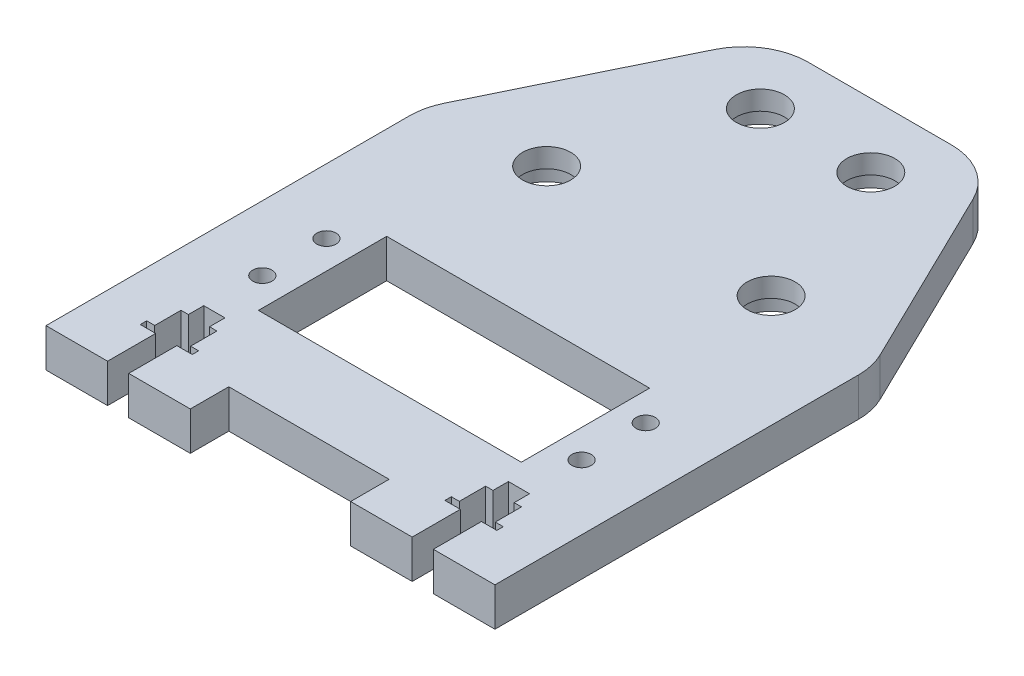
SolidWorks part; units mm, degrees
material "Acrylic (Medium-high impact)"
ref_plane "Front Plane" through (0, 0, 0) normal (0, 0, 1) x (1, 0, 0)
ref_plane "Top Plane" through (0, 0, 0) normal (0, 1, 0) x (1, 0, 0)
ref_plane "Right Plane" through (0, 0, 0) normal (1, 0, 0) x (0, 0, -1)
sketch "Sketch1" plane through (0, 0, 0) normal (0, 1, 0) x (1, 0, 0)
  line L0 (0, 16.0328) -> (0, -11.4098) construction
  line L1 (-38.0739, 0) -> (41.7971, 0) construction
  line L2 (8.6075, -9.22) -> (17.5, -33.652) construction
  line L3 (-8.6075, -9.22) -> (-17.5, -33.652) construction
  line L4 (17.5, -33.652) -> (10.3, -65.6008) construction
  line L5 (24.8896, -70.6008) -> (-24.8896, -70.6008) construction
  line L6 (-17.4416, 0.78) -> (-35, -35.22)
  line L7 (-35, -94.22) -> (35, -94.22)
  line L8 (-35, -94.22) -> (-35, 0.78)
  line L9 (-35, 0.78) -> (35, 0.78)
  line L10 (35, -94.22) -> (35, 0.78)
  line L11 (-35, -94.22) -> (35, 0.78) construction
  line L12 (-35, 0.78) -> (35, -94.22) construction
  line L13 (17.4416, 0.78) -> (35, -35.22)
  line L15 (-12.5, -88.22) -> (12.5, -88.22)
  line L16 (-12.5, -88.22) -> (-12.5, -94.22)
  line L17 (-12.5, -94.22) -> (12.5, -94.22)
  line L18 (12.5, -88.22) -> (12.5, -94.22)
  line L19 (-12.5, -88.22) -> (12.5, -94.22) construction
  line L20 (-12.5, -94.22) -> (12.5, -88.22) construction
  line L21 (20.5, -55.6008) -> (-20.5, -55.6008)
  line L22 (20.5, -55.6008) -> (20.5, -75.6008)
  line L23 (20.5, -75.6008) -> (-20.5, -75.6008)
  line L24 (-20.5, -55.6008) -> (-20.5, -75.6008)
  line L25 (20.5, -55.6008) -> (-20.5, -75.6008) construction
  line L26 (20.5, -75.6008) -> (-20.5, -55.6008) construction
  circle A0 centre (17.5, -33.652) radius 23.625 construction
  circle A1 centre (-8.6075, -9.22) radius 3.75
  circle A2 centre (-17.5, -33.652) radius 3.75
  circle A3 centre (17.5, -33.652) radius 3.75
  circle A4 centre (8.6075, -9.22) radius 3.75
  circle A5 centre (10.3, -65.6008) radius 3.75
  circle A6 centre (8.6075, -9.22) radius 5.5
  circle A7 centre (-8.6075, -9.22) radius 5.5
  circle A8 centre (-17.5, -33.652) radius 5.5
  circle A9 centre (17.5, -33.652) radius 5.5
  point P18 (0, -46.72)
  point P28 (0, -91.22)
  point P37 (0, -65.6008)
  arc B0 (3.9, -65.6008) -> (16.7, -65.6008) centre (10.3, -65.6008) ccw construction
  arc B1 (26.7, -59.3508) -> (22.6896, -60.6008) centre (24.8896, -60.6008) ccw construction
  arc B2 (22.6896, -70.6008) -> (26.7, -71.8508) centre (24.8896, -70.6008) ccw construction
  arc B3 (-26.7, -61.8508) -> (-26.7, -59.3508) centre (-24.8896, -60.6008) ccw construction
  arc B4 (-26.7, -71.8508) -> (-26.7, -69.3508) centre (-24.8896, -70.6008) ccw construction
  circle B5 centre (10.3, -65.6008) radius 6.5
  circle B6 centre (24.8896, -60.6008) radius 1.5
  circle B7 centre (24.8896, -70.6008) radius 1.5
  circle B8 centre (-24.8896, -70.6008) radius 1.5
  circle B9 centre (-24.8896, -60.6008) radius 1.5
  dimension "D5" = 47.25
  dimension "D7" = 7.5
  dimension "D15" = 11
  dimension "D1" = 35
  dimension "D2" = 26
  dimension "D3" = 160
  dimension "D4" = 9.22
  dimension "D6" = 32.75
  dimension "D8" = 95
  dimension "D9" = 70
  dimension "D10" = 10
  dimension "D11" = 26
  dimension "D12" = 59
  dimension "D13" = 25
  dimension "D14" = 6
  dimension "D16" = 41
  dimension "D17" = 20
  dimension "D18" = 10.3
sketch_block_instance "Block1-1"
sketch_block "Block1" parameters "D1"=3, "D2"=13
ref_axis "Axis1" through (17.5, 0, 33.652) along (0, 1, 0)
ref_axis "Axis2" through (-17.5, -6.1694, 33.652) along (0, 1, 0)
ref_axis "Axis3" through (10.3, 0, 65.6008) along (0, 1, 0)
extrude "Boss-Extrude1" add sketch "Sketch1" along normal blind 6 contours L15 L18 L7 L10 L13 L9 L6 L8 L16 B9 B8 B7 B6 B5 A4 A3 A2 A1 | B5 A5 | L21 L24 L23 L22 B9 B8 B5 region at (0, 0, 48.7374) region at (-1.9892, 0, 65.6008) region at (3.9838, 0, 65.6008)
fillet "Fillet1" radius 10 4 edges at (35, 3, 35.22) (17.4416, 3, -0.78) (-17.4416, 3, -0.78) (-35, 3, 35.22)
sketch "Sketch2" plane through (0, 6, 0) normal (0, 1, 0) x (1, 0, 0)
  circle A0 centre (24.8896, -60.6008) radius 4
  circle A1 centre (24.8896, -70.6008) radius 4
  circle A2 centre (-24.8896, -60.6008) radius 4
  circle A3 centre (-24.8896, -70.6008) radius 4
  dimension "D1" = 8
extrude "Boss-Extrude2" add sketch "Sketch1<3>" against normal blind 3 from surface contours A8 A2 | A7 A1 | A9 A3 | A6 A4 region at (3.263, 0, 9.22) region at (-13.9519, 0, 9.22) region at (-22.8444, 0, 33.652) region at (12.1556, 0, 33.652) starting at face at (-24.8896, 6, 62.1008)
sketch "Sketch1<3>" plane through (0, 0, 0) normal (0, 1, 0) x (1, 0, 0) same geometry as "Sketch1"
extrude "Cut-Extrude2" cut sketch "Sketch1<4>" along normal blind 10 contours L23 L24 L21 L22
sketch "Sketch1<4>" plane through (0, 0, 0) normal (0, 1, 0) x (1, 0, 0) same geometry as "Sketch1"
sketch "Sketch4" plane through (0, 0, 0) normal (0, -1, 0) x (1, 0, 0)
  line L0 (-23.75, 94.22) -> (-23.75, 80.2366) construction
  line L1 (-35, 94.22) -> (-12.5, 94.22) construction
  line L2 (-12.5, 88.22) -> (12.5, 88.22) construction
  line L3 (-22.1, 79.22) -> (-25.4, 79.22)
  line L4 (-22.1, 79.22) -> (-22.1, 94.22)
  line L5 (-22.1, 94.22) -> (-25.4, 94.22)
  line L6 (-25.4, 79.22) -> (-25.4, 94.22)
  line L7 (-22.1, 79.22) -> (-25.4, 94.22) construction
  line L8 (-22.1, 94.22) -> (-25.4, 79.22) construction
  line L9 (-20.95, 81.62) -> (-26.55, 81.62)
  line L10 (-20.95, 81.62) -> (-20.95, 85.72)
  line L11 (-20.95, 85.72) -> (-26.55, 85.72)
  line L12 (-26.55, 81.62) -> (-26.55, 85.72)
  line L13 (-20.95, 81.62) -> (-26.55, 85.72) construction
  line L14 (-20.95, 85.72) -> (-26.55, 81.62) construction
  line L15 (-19.7, 86.72) -> (-27.8, 86.72)
  line L16 (-19.7, 86.72) -> (-19.7, 85.72)
  line L17 (-19.7, 85.72) -> (-27.8, 85.72)
  line L18 (-27.8, 86.72) -> (-27.8, 85.72)
  line L19 (-19.7, 86.72) -> (-27.8, 85.72) construction
  line L20 (-19.7, 85.72) -> (-27.8, 86.72) construction
  point P4 (-23.75, 86.72)
  point P9 (-23.75, 83.67)
  point P14 (-23.75, 86.22)
  point P19 (-19.7, 86.1569)
  dimension "D1" = 3.3
  dimension "D2" = 15
  dimension "D3" = 5.6
  dimension "D4" = 8.1
  dimension "D5" = 1
  dimension "D6" = 4.1
  dimension "D7" = 1.5
extrude "Cut-Extrude3" cut sketch "Sketch4" against normal blind 10 contours L4 L5 L6 L3 | L15 L18 L17 L16 | L10 L11 L12 L9
mirror "Mirror1" about plane through (0, 0, 0) normal (1, 0, 0) of "Cut-Extrude3"
